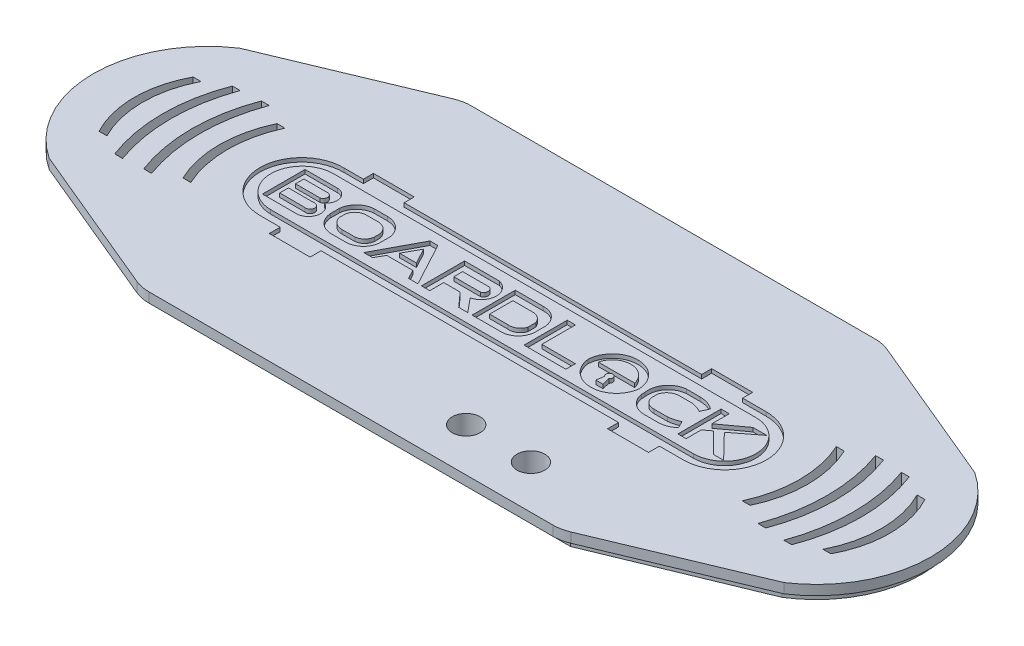
SolidWorks part; units mm, degrees
ref_plane "Front Plane" through (0, 0, 0) normal (0, 0, 1) x (1, 0, 0)
ref_plane "Top Plane" through (0, 0, 0) normal (0, 1, 0) x (1, 0, 0)
ref_plane "Right Plane" through (0, 0, 0) normal (1, 0, 0) x (0, 0, -1)
sketch "Sketch2" plane through (0, 0, 0) normal (0, 1, 0) x (1, 0, 0)
  line L0 (0, 0) -> (102, 0) construction
  line L1 (0, 0) -> (0, -77.2) construction
  line L2 (102, 0) -> (102, -77.2) construction
  line L3 (0, -77.2) -> (102, -77.2) construction
  line L4 (51, 0) -> (51, -77.2) construction
  line L5 (0, -38.6) -> (102, -38.6) construction
  line L6 (-2.5, 2.5) -> (104.5, 2.5)
  line L7 (-2.5, -79.7) -> (104.5, -79.7)
  line L8 (104.5, 2.5) -> (144.7372, -14.2911)
  line L9 (104.5, -79.7) -> (144.7372, -62.9089)
  line L10 (102, -38.6) -> (155.3, -38.6) construction
  line L11 (-2.5, -79.7) -> (-42.7372, -62.9089)
  line L12 (-2.5, 2.5) -> (-42.7372, -14.2911)
  line L13 (0, 0) -> (102, 0)
  line L14 (102, 0) -> (104.5, 0)
  line L15 (104.5, 0) -> (142.7026, -15.7437)
  line L16 (104.5, -77.2) -> (142.7026, -61.4563)
  line L17 (102, -77.2) -> (104.5, -77.2)
  line L18 (-2.5, -77.2) -> (-40.7026, -61.4563)
  line L19 (0, -77.2) -> (-2.5, -77.2)
  line L20 (-2.5, 0) -> (-40.7026, -15.7437)
  line L21 (0, 0) -> (-2.5, 0)
  line L22 (0, -77.2) -> (102, -77.2)
  line L23 (0.5, 0) -> (0.5, -77.2) construction
  line L24 (0, -76.7) -> (97.7329, -76.7) construction
  line L25 (0.5, -74.6) -> (97.3633, -74.6) construction
  line L26 (63.32, -77.2) -> (63.32, 0) construction
  line L27 (0.5, -62.6) -> (97.044, -62.6) construction
  line L28 (75.32, -62.6) -> (75.32, -74.6) construction
  line L29 (79.83, -62.6) -> (79.83, -74.6) construction
  line L30 (91.83, -62.6) -> (91.83, -74.6) construction
  line L31 (69.32, -62.6) -> (69.32, -74.6) construction
  line L32 (63.32, -68.6) -> (75.32, -68.6) construction
  line L33 (85.83, -62.6) -> (85.83, -74.6) construction
  line L34 (79.83, -68.6) -> (91.83, -68.6) construction
  arc A0 (144.7372, -14.2911) -> (144.7372, -62.9089) centre (128.65, -38.6) cw
  arc A1 (-42.7372, -14.2911) -> (-42.7372, -62.9089) centre (-26.65, -38.6) ccw
  arc A2 (142.7026, -15.7437) -> (142.7026, -61.4563) centre (128.65, -38.6) cw
  arc A3 (-40.7026, -15.7437) -> (-40.7026, -61.4563) centre (-26.65, -38.6) ccw
  circle A4 centre (69.32, -68.6) radius 3.55
  circle A5 centre (85.83, -68.6) radius 3.55
  point P16 (157.8, -38.6)
  dimension "D3" = 2.5
  dimension "D10" = 2.5
  dimension "D1" = 77.2
  dimension "D2" = 102
  dimension "D4" = 2.5
  dimension "D5" = 2.5
  dimension "D6" = 2.5
  dimension "D7" = 0.5
  dimension "D8" = 2.5
  dimension "D9" = 53.3
  dimension "D11" = 0.5
  dimension "D12" = 2.1
  dimension "D13" = 62.82
  dimension "D14" = 12
  dimension "D15" = 12
  dimension "D16" = 4.51
  dimension "D17" = 12
  dimension "D18" = 6
  dimension "D19" = 6
  dimension "D20" = 6
  dimension "D21" = 6
extrude "Boss-Extrude3" add sketch "Sketch2" along normal blind 2.5 contours L6 L8 A0 L9 L7 L11 A1 L12
extrude "Boss-Extrude4" add sketch "Sketch2<8>" against normal blind 2.5 contours L20 A3 L18 L19 L22 L17 L16 A2 L15 L14 L13 L21 region at (50.8464, 0, 38.4266)
sketch "Sketch2<8>" plane through (0, 0, 0) normal (0, 1, 0) x (1, 0, 0) same geometry as "Sketch2"
sketch "Sketch3" plane through (0, 2.5, 0) normal (0, 1, 0) x (1, 0, 0)
  line L0 (-55.8, -38.6) -> (157.8, -38.6) construction
  line L1 (51, 2.5) -> (51, -79.7) construction
  line L2 (-2.5, 2.5) -> (104.5, 2.5) construction
  line L3 (-2.5, -79.7) -> (104.5, -79.7) construction
  line L4 (201.4283, 144.6262) -> (1084.095, 144.6262) construction
  line L5 (-2.9873, -27.462) -> (1.9495, -27.462)
  line L6 (1.9495, -27.462) -> (1.9495, -24.9021)
  line L7 (1.9495, -24.9021) -> (12.3717, -24.9021)
  line L8 (12.3717, -24.9021) -> (12.3717, -27.462)
  line L9 (12.3717, -27.462) -> (88.2398, -27.462)
  line L10 (88.2398, -27.462) -> (88.2398, -24.9021)
  line L11 (88.2398, -24.9021) -> (98.6886, -24.9021)
  line L12 (98.6886, -24.9021) -> (98.6886, -27.462)
  line L13 (98.6886, -27.462) -> (104.6245, -27.462)
  line L14 (104.6245, -48.6746) -> (98.6886, -48.6746)
  line L15 (98.6886, -48.6746) -> (98.6886, -51.4646)
  line L16 (98.6886, -51.4646) -> (88.2398, -51.4646)
  line L17 (88.2398, -51.4646) -> (88.2398, -48.6746)
  line L18 (88.2398, -48.6746) -> (12.3717, -48.6746)
  line L19 (12.3717, -48.6746) -> (12.3717, -51.4646)
  line L20 (12.3717, -51.4646) -> (1.9495, -51.4646)
  line L21 (1.9495, -51.4646) -> (1.9495, -48.6746)
  line L22 (1.9495, -48.6746) -> (-2.9873, -48.6746)
  line L23 (-2.9873, -30.0692) -> (104.7002, -30.0692)
  line L24 (104.7002, -46.0158) -> (-3.1948, -46.0158)
  line L25 (-7.6306, -32.7625) -> (-7.6306, -43.6232)
  line L26 (-7.6306, -43.6232) -> (1.1441, -43.6232)
  line L27 (-7.6306, -32.7625) -> (0.7133, -32.7625)
  line L28 (5.3465, -39.2139) -> (5.3465, -36.9174)
  line L29 (-5.6807, -35.0072) -> (0.6, -35.0072)
  line L30 (-5.6807, -35.0072) -> (-5.6807, -37.1385)
  line L31 (-5.6807, -37.1385) -> (0.6, -37.1385)
  line L33 (-5.6807, -38.9524) -> (0.7133, -38.9524)
  line L34 (-5.6807, -38.9524) -> (-5.6807, -41.1744)
  line L35 (-5.6807, -41.1744) -> (0.7133, -41.1744)
  line L41 (10.1371, -35.0072) -> (13.3467, -35.0072)
  line L42 (9.866, -32.6184) -> (13.2281, -32.6184)
  line L43 (18.2229, -43.6232) -> (20.4629, -43.6232)
  line L44 (18.0967, -36.7888) -> (18.0967, -39.563)
  line L45 (16.1379, -37.4286) -> (16.1379, -38.7874)
  line L46 (13.8283, -43.6232) -> (10.2518, -43.6232)
  line L47 (20.4629, -43.6232) -> (21.7662, -41.3167)
  line L48 (13.6087, -41.3167) -> (10.2917, -41.3167)
  line L49 (21.7662, -41.3167) -> (28.4046, -41.3167)
  line L50 (7.3404, -38.9659) -> (7.3404, -37.4286)
  line L51 (28.4046, -41.3167) -> (29.6467, -43.6232)
  line L52 (29.6467, -43.6232) -> (32.0292, -43.6232)
  line L53 (32.0292, -43.6232) -> (26.1026, -32.6184)
  line L54 (26.1026, -32.6184) -> (24.0876, -32.6184)
  line L55 (24.0876, -32.6184) -> (18.2229, -43.6232)
  line L56 (22.9065, -39.2139) -> (27.2439, -39.2139)
  line L57 (27.2439, -39.2139) -> (25.0951, -35.224)
  line L58 (25.0951, -35.224) -> (22.9065, -39.2139)
  line L59 (32.928, -32.6184) -> (32.928, -43.6232)
  line L60 (32.928, -43.6232) -> (35.043, -43.6232)
  line L61 (35.043, -43.6232) -> (35.043, -40.0634)
  line L62 (35.043, -40.0634) -> (39.244, -40.0634)
  line L63 (39.244, -40.0634) -> (42.431, -43.6232)
  line L64 (42.431, -43.6232) -> (44.7378, -43.6232)
  line L65 (44.7378, -43.6232) -> (41.7936, -40.0634)
  line L66 (32.928, -32.6184) -> (41.7936, -32.6184)
  line L67 (35.043, -35.224) -> (35.043, -37.4805)
  line L68 (35.043, -37.4805) -> (41.7936, -37.4805)
  line L69 (35.043, -35.224) -> (41.7936, -35.224)
  line L70 (45.8463, -32.6184) -> (45.8463, -43.6232)
  line L71 (45.8463, -43.6232) -> (52.8329, -43.6232)
  line L72 (45.8463, -32.6184) -> (52.9687, -32.6184)
  line L73 (57.6458, -36.7888) -> (57.6458, -39.563)
  line L74 (47.8647, -35.224) -> (47.8647, -41.1744)
  line L75 (47.8647, -41.1744) -> (52.6, -41.1744)
  line L76 (47.8647, -35.224) -> (52.6, -35.224)
  line L77 (55.6246, -37.1385) -> (55.6246, -39.1866)
  line L78 (59.1096, -32.6184) -> (59.1096, -43.6232)
  line L79 (59.1096, -43.6232) -> (69.7525, -43.6232)
  line L80 (69.7525, -43.6232) -> (69.7525, -41.1876)
  line L81 (69.7525, -41.1876) -> (61.1954, -41.1876)
  line L82 (61.1954, -41.1876) -> (61.1954, -32.6184)
  line L83 (61.1954, -32.6184) -> (59.1096, -32.6184)
  line L84 (72.3273, -37.9056) -> (81.6057, -37.9056)
  line L85 (76.285, -40.2528) -> (75.9572, -42.1923)
  line L86 (75.9572, -42.1923) -> (77.8461, -42.1923)
  line L87 (77.8461, -42.1923) -> (77.3335, -40.2528)
  line L88 (90.3322, -35.0072) -> (93.3549, -35.0072)
  line L89 (96.0824, -35.9398) -> (96.9798, -33.9561)
  line L90 (92.9888, -32.6184) -> (89.5293, -32.6184)
  line L91 (86.9671, -37.333) -> (86.9671, -38.6)
  line L92 (86.9671, -38.6) -> (86.9671, -39.0585)
  line L93 (89.7665, -41.1876) -> (93.2664, -41.1876)
  line L94 (96.1597, -40.3804) -> (97.0399, -42.1923)
  line L95 (93.0498, -43.6232) -> (90.1278, -43.6232)
  line L96 (84.9417, -38.6) -> (84.9417, -39.5139)
  line L97 (98.3461, -32.6195) -> (98.3461, -43.6259)
  line L98 (98.3461, -43.6259) -> (100.4335, -43.6259)
  line L99 (100.4335, -43.6259) -> (100.4335, -39.7387)
  line L100 (100.4335, -39.7387) -> (102.2231, -38.4318)
  line L101 (102.2231, -38.4318) -> (107.3754, -43.6259)
  line L102 (107.3754, -43.6259) -> (110.0073, -43.6259)
  line L103 (110.0073, -43.6259) -> (103.904, -37.333)
  line L104 (103.904, -37.333) -> (110.0073, -32.6195)
  line L105 (110.0073, -32.6195) -> (106.4905, -32.6195)
  line L106 (106.4905, -32.6195) -> (100.4335, -37.0424)
  line L107 (100.4335, -37.0424) -> (100.4335, -32.6195)
  line L108 (100.4335, -32.6195) -> (98.3461, -32.6195)
  arc A0 (86.9671, -37.333) -> (90.3322, -35.0072) centre (90.1278, -38.3088) cw
  arc A1 (93.3549, -35.0072) -> (96.0824, -35.9398) centre (92.5616, -41.7819) cw
  arc A2 (-42.7372, -14.2911) -> (-42.7372, -62.9089) centre (-26.65, -38.6) ccw construction
  arc A3 (144.7372, -62.9089) -> (144.7372, -14.2911) centre (128.65, -38.6) ccw construction
  arc A4 (-2.9873, -27.462) -> (-2.9873, -48.6746) centre (-3.1948, -38.0683) ccw
  arc A5 (104.6245, -27.462) -> (104.6245, -48.6746) centre (104.776, -38.0683) cw
  arc A6 (-2.9873, -30.0692) -> (-3.1948, -46.0158) centre (-3.091, -38.0425) ccw
  arc A7 (104.7002, -30.0692) -> (104.7002, -46.0158) centre (104.7002, -38.0425) cw
  arc A8 (0.7133, -32.7625) -> (2.2325, -37.6827) centre (0.6, -35.492) cw
  arc A9 (1.1441, -43.6232) -> (2.2325, -37.6827) centre (1.0303, -40.5324) ccw
  arc A10 (0.6, -35.0072) -> (0.6, -37.1385) centre (0.3019, -36.0728) cw
  arc A11 (0.7133, -41.1744) -> (0.7133, -38.9524) centre (0.9838, -40.0634) ccw
  arc A12 (5.3465, -36.9174) -> (9.866, -32.6184) centre (10.1371, -37.4286) cw
  arc A13 (18.0967, -36.7888) -> (13.2281, -32.6184) centre (13.2836, -37.4805) ccw
  arc A14 (5.3465, -39.2139) -> (10.2518, -43.6232) centre (10.0037, -38.9659) ccw
  arc A15 (13.8283, -43.6232) -> (18.0967, -39.563) centre (13.6087, -39.1187) ccw
  arc A16 (10.1371, -35.0072) -> (7.3404, -37.4286) centre (10.2483, -37.9613) ccw
  arc A17 (13.3467, -35.0072) -> (16.1379, -37.4286) centre (13.2781, -37.9056) cw
  arc A18 (16.1379, -38.7874) -> (13.6087, -41.3167) centre (13.3904, -38.5692) cw
  arc A19 (10.2917, -41.3167) -> (7.3404, -38.9659) centre (10.2917, -38.2887) cw
  arc A20 (41.7936, -35.224) -> (41.7936, -37.4805) centre (41.488, -36.3523) cw
  arc A21 (41.7936, -40.0634) -> (41.7936, -32.6184) centre (40.9073, -36.3409) ccw
  arc A22 (52.9687, -32.6184) -> (57.6458, -36.7888) centre (53.222, -37.0421) cw
  arc A23 (57.6458, -39.563) -> (52.8329, -43.6232) centre (53.2093, -39.1866) cw
  arc A24 (52.6, -35.224) -> (55.6246, -37.1385) centre (52.8789, -38.1299) cw
  arc A25 (55.6246, -39.1866) -> (52.6, -41.1744) centre (52.8755, -38.2986) cw
  arc A26 (70.3877, -38.6) -> (83.4404, -38.6) centre (76.9141, -38.8997) cw
  arc A27 (70.3877, -38.6) -> (83.4404, -38.6) centre (76.9141, -37.8504) ccw
  arc A28 (76.285, -40.2528) -> (77.3335, -40.2528) centre (76.8092, -39.581) cw
  arc A29 (72.3273, -37.9056) -> (81.6057, -37.9056) centre (76.9665, -38.9919) cw
  arc A30 (96.9798, -33.9561) -> (92.9888, -32.6184) centre (93.0498, -39.0585) ccw
  arc A31 (89.5293, -32.6184) -> (84.9417, -38.6) centre (89.9999, -37.7293) ccw
  arc A32 (86.9671, -39.0585) -> (89.7665, -41.1876) centre (89.6538, -38.4308) ccw
  arc A33 (93.2664, -41.1876) -> (96.1597, -40.3804) centre (92.4973, -32.8415) ccw
  arc A34 (84.9417, -39.5139) -> (90.1278, -43.6232) centre (89.7907, -38.7214) ccw
  arc A35 (93.0498, -43.6232) -> (97.0399, -42.1923) centre (93.1901, -37.7354) ccw
extrude "Logo" cut sketch "Sketch3" against normal blind 1 contours L26 A9 A8 L27 L25 A11 L35 L34 L33 L29 A10 L31 L30 | L46 A15 L44 A13 L42 A12 L28 A14 L48 A19 L50 A16 L41 A17 L45 A18 | L54 L55 L43 L47 L49 L51 L52 L53 L58 L57 L56 | L65 A21 L66 L59 L60 L61 L62 L63 L64 L69 A20 L68 L67 | A23 L73 A22 L72 L70 L71 L77 A25 L75 L74 L76 A24 | A26 A27 L85 A28 L87 L86 L84 A29 | L95 A35 L94 A33 L93 A32 L92 L91 A0 L88 A1 L89 A30 L90 A31 L96 A34 | L107 L108 L97 L98 L99 L100 L101 L102 L103 L104 L105 L106 | L82 L83 L78 L79 L80 L81 | A4 L22 L21 L20 L19 L18 L17 L16 L15 L14 A5 L13 L12 L11 L10 L9 L8 L7 L6 L5 | A6 L24 A7 L23 | L78 L79 L80 L81 L82 L83 region at (-2.2321, 2.5, 38.3038) region at (5.5149, 2.5, 38.0657) region at (21.3111, 2.5, 38.2038) region at (37.3608, 2.5, 32.7798) region at (49.4075, 2.5, 32.7799) region at (60.1525, 2.5, 32.7715) region at (88.1536, 2.5, 35.4525) region at (102.8661, 2.5, 37.8921) region at (76.9141, 2.5, 32.5442)
fillet "Fillet1" radius 10 4 edges at (-2.5, 1.25, -2.5) (104.5, 1.25, -2.5) (104.5, 1.25, 79.7) (-2.5, 1.25, 79.7)
sketch "Sketch4" plane through (0, 2.5, 0) normal (0, 1, 0) x (1, 0, 0)
  line L0 (-55.8, -38.6) -> (157.8, -38.6) construction
  line L1 (51, 2.5) -> (51, -79.7) construction
  line L2 (-0.4972, 2.5) -> (102.4972, 2.5) construction
  line L3 (-0.4972, -79.7) -> (102.4972, -79.7) construction
  line L4 (-42.3364, -26.6) -> (-42.3364, -50.6) construction
  line L5 (-40.3364, -26.6) -> (-40.3364, -50.6) construction
  line L6 (-35.3364, -23.6) -> (-35.3364, -53.6) construction
  line L7 (-33.3364, -23.6) -> (-33.3364, -53.6) construction
  line L8 (-28.3364, -23.2) -> (-28.3364, -53.2) construction
  line L9 (-26.3364, -23.2) -> (-26.3364, -53.2) construction
  line L10 (-21.3364, -26.2) -> (-21.3364, -50.2) construction
  line L11 (-19.3364, -26.2) -> (-19.3364, -50.2) construction
  line L12 (-42.3364, -26.6) -> (-40.3364, -26.6)
  line L13 (-42.3364, -50.6) -> (-40.3364, -50.6)
  line L14 (-35.3364, -53.6) -> (-33.3364, -53.6)
  line L15 (-35.3364, -23.6) -> (-33.3364, -23.6)
  line L16 (-28.3364, -23.2) -> (-26.3364, -23.2)
  line L17 (-28.3364, -53.2) -> (-26.3364, -53.2)
  line L18 (-21.3364, -50.2) -> (-19.3364, -50.2)
  line L19 (-21.3364, -26.2) -> (-19.3364, -26.2)
  line L20 (121.3364, -26.2) -> (121.3364, -50.2) construction
  line L21 (123.3364, -26.2) -> (123.3364, -50.2) construction
  line L22 (128.3364, -23.2) -> (128.3364, -53.2) construction
  line L23 (130.3364, -23.2) -> (130.3364, -53.2) construction
  line L24 (135.3364, -23.6) -> (135.3364, -53.6) construction
  line L25 (137.3364, -23.6) -> (137.3364, -53.6) construction
  line L26 (142.3364, -26.6) -> (142.3364, -50.6) construction
  line L27 (144.3364, -26.6) -> (144.3364, -50.6) construction
  line L28 (123.3364, -26.2) -> (121.3364, -26.2)
  line L29 (123.3364, -50.2) -> (121.3364, -50.2)
  line L30 (130.3364, -53.2) -> (128.3364, -53.2)
  line L31 (130.3364, -23.2) -> (128.3364, -23.2)
  line L32 (137.3364, -23.6) -> (135.3364, -23.6)
  line L33 (137.3364, -53.6) -> (135.3364, -53.6)
  line L34 (144.3364, -50.6) -> (142.3364, -50.6)
  line L35 (144.3364, -26.6) -> (142.3364, -26.6)
  arc A0 (-42.7372, -14.2911) -> (-42.7372, -62.9089) centre (-26.65, -38.6) ccw construction
  arc A1 (144.7372, -62.9089) -> (144.7372, -14.2911) centre (128.65, -38.6) ccw construction
  arc A2 (-42.3364, -26.6) -> (-42.3364, -50.6) centre (-19.91, -38.6) ccw
  arc A3 (-40.3364, -26.6) -> (-40.3364, -50.6) centre (-16.7181, -38.6) ccw
  arc A4 (-35.3364, -23.6) -> (-35.3364, -53.6) centre (3.8054, -38.6) ccw
  arc A5 (-33.3364, -53.6) -> (-33.3364, -23.6) centre (8.2465, -38.6) cw
  arc A6 (-28.3364, -23.2) -> (-28.3364, -53.2) centre (11.3609, -38.2) ccw
  arc A7 (-26.3364, -23.2) -> (-26.3364, -53.2) centre (14.8909, -38.2) ccw
  arc A8 (-21.3364, -26.2) -> (-21.3364, -50.2) centre (3.9499, -38.2) ccw
  arc A9 (-19.3364, -26.2) -> (-19.3364, -50.2) centre (6.9686, -38.2) ccw
  arc A10 (121.3364, -26.2) -> (121.3364, -50.2) centre (95.0314, -38.2) cw
  arc A11 (123.3364, -26.2) -> (123.3364, -50.2) centre (98.0501, -38.2) cw
  arc A12 (128.3364, -23.2) -> (128.3364, -53.2) centre (87.1091, -38.2) cw
  arc A13 (130.3364, -23.2) -> (130.3364, -53.2) centre (90.6391, -38.2) cw
  arc A14 (135.3364, -53.6) -> (135.3364, -23.6) centre (93.7535, -38.6) ccw
  arc A15 (137.3364, -23.6) -> (137.3364, -53.6) centre (98.1946, -38.6) cw
  arc A16 (142.3364, -26.6) -> (142.3364, -50.6) centre (118.7181, -38.6) cw
  arc A17 (144.3364, -26.6) -> (144.3364, -50.6) centre (121.91, -38.6) cw
  dimension "D1" = 24
  dimension "D2" = 12
  dimension "D3" = 30
  dimension "D4" = 15
  dimension "D5" = 2
  dimension "D6" = 2
  dimension "D7" = 2
  dimension "D8" = 2
  dimension "D9" = 7
  dimension "D10" = 7
  dimension "D11" = 7
extrude "SoundGaps" cut sketch "Sketch4" against normal up to next
sketch "Sketch5" plane through (0, 2.5, 0) normal (0, 1, 0) x (1, 0, 0)
  circle A2 centre (69.32, -68.6) radius 3.55
  circle A3 centre (85.83, -68.6) radius 3.55
extrude "Buttons" cut sketch "Sketch5" against normal up to next
